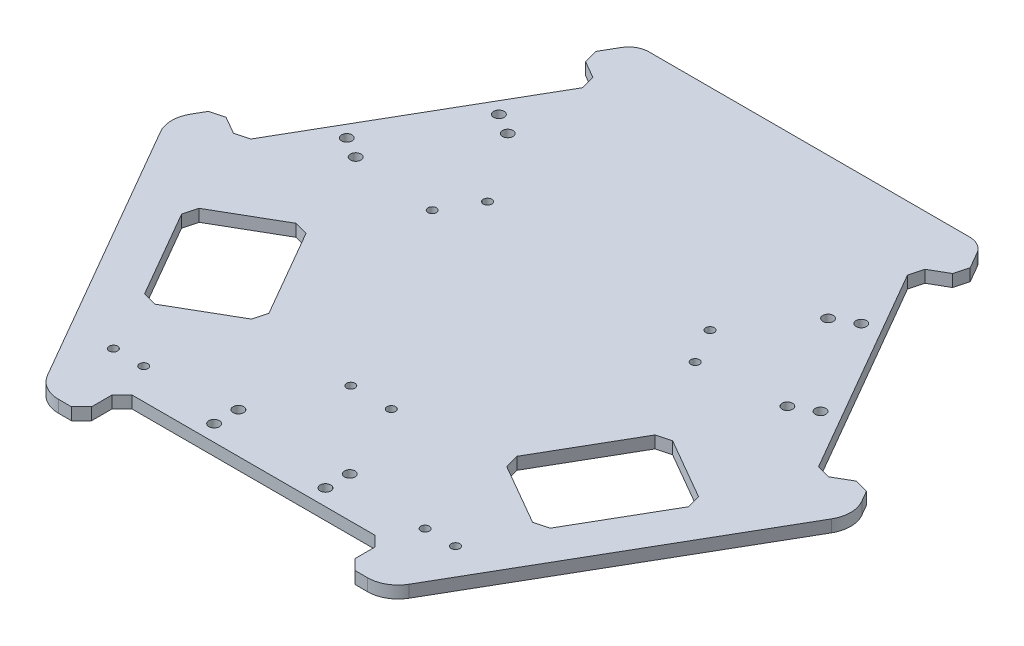
SolidWorks part; units mm, degrees
material "5052-H32"
ref_plane "前基準面" through (0, 0, 0) normal (0, 0, 1) x (1, 0, 0)
ref_plane "上基準面" through (0, 0, 0) normal (0, 1, 0) x (1, 0, 0)
ref_plane "右基準面" through (0, 0, 0) normal (1, 0, 0) x (0, 0, -1)
sketch "草圖1" plane through (0, 0, 0) normal (0, 1, 0) x (1, 0, 0)
  line L1 (85, 147.2243) -> (-85, 147.2243)
  line L2 (-85, 147.2243) -> (-170, 0)
  line L3 (-170, 0) -> (-85, -147.2243)
  line L4 (-85, -147.2243) -> (85, -147.2243)
  line L5 (85, -147.2243) -> (170, 0)
  line L6 (170, 0) -> (85, 147.2243)
  circle A0 centre (0, 0) radius 147.2243 construction
  dimension "D1" = 170
extrude "填料-伸長1" add sketch "草圖1" along normal blind 6
ref_axis "基準軸1" through (0, 5.25, 0) along (0, -1, 0)
sketch "草圖16" plane through (0, 6, 0) normal (0, 1, 0) x (1, 0, 0)
  line L0 (-65, -147.2243) -> (65, -147.2243)
  line L1 (-65, -147.2243) -> (-65, -127.2243)
  line L2 (65, -147.2243) -> (65, -127.2243)
  line L3 (-65, -127.2243) -> (65, -127.2243)
  line L4 (-85, -147.2243) -> (85, -147.2243) construction
  point P6 (0, -147.2243)
  point P7 (0, -147.2243)
  dimension "D1" = 20
  dimension "D2" = 130
extrude "除料-伸長16" cut sketch "草圖16" against normal blind 10
sketch "草圖9" plane through (0, 6, 0) normal (0, 1, 0) x (1, 0, 0)
  line L0 (-27.5, -107.2243) -> (27.5, -107.2243) construction
  line L1 (27.5, -107.2243) -> (27.5, -119.2243) construction
  line L2 (-27.5, -107.2243) -> (-27.5, -119.2243) construction
  line L3 (-27.5, -119.2243) -> (27.5, -119.2243) construction
  line L4 (65, -127.2243) -> (-65, -127.2243) construction
  circle A0 centre (-27.5, -119.2243) radius 2.6
  circle A1 centre (-27.5, -107.2243) radius 2.6
  circle A2 centre (27.5, -107.2243) radius 2.6
  circle A3 centre (27.5, -119.2243) radius 2.6
  point P8 (-36.6057, -114.7334)
  point P11 (0, -119.2243)
  point P12 (0, -127.2243)
  dimension "D1" = 5.2
  dimension "D2" = 12
  dimension "D3" = 8
  dimension "D4" = 55
extrude "除料-伸長8" cut sketch "草圖9" against normal through all and the other way through all
sketch "草圖18" plane through (0, 6, 0) normal (0, 1, 0) x (1, 0, 0)
  line L0 (-10, -69.2243) -> (10, -69.2243) construction
  line L1 (65, -127.2243) -> (-65, -127.2243) construction
  circle A0 centre (-10, -69.2243) radius 2.1
  circle A1 centre (10, -69.2243) radius 2.1
  point P4 (0, -69.2243)
  point P7 (0, -127.2243)
  dimension "D3" = 4.2
  dimension "D4" = 4.2
  dimension "D1" = 20
  dimension "D2" = 58
extrude "除料-伸長17" cut sketch "草圖18" against normal up to next
pattern_circular "環狀複製排列1" count 3 over 360 about axis through (0, 5.25, 0) along (0, -1, 0) of "除料-伸長8", "除料-伸長16", "除料-伸長17"
chamfer "導角4" distance 5 angle 45 12 edges at (65, 3, 127.2243) (65, 3, 147.2243) (-65, 3, 147.2243) (-65, 3, 127.2243) (77.6795, 3, -119.9038) (95, 3, -129.9038) (160, 3, -17.3205) (142.6795, 3, -7.3205) (-142.6795, 3, -7.3205) (-160, 3, -17.3205) (-95, 3, -129.9038) (-77.6795, 3, -119.9038)
sketch "草圖5" plane through (0, 6, 0) normal (0, 1, 0) x (1, 0, 0)
  line L0 (0, 0) -> (0, -112) construction
  line L1 (0, -112) -> (-77, -112) construction
  line L2 (-84.5, -112) -> (-69.5, -112) construction
  circle A0 centre (-84.5, -112) radius 2.1
  circle A1 centre (-69.5, -112) radius 2.1
  circle A2 centre (84.5, -112) radius 2.1
  circle A3 centre (69.5, -112) radius 2.1
  point P8 (-77, -112)
  dimension "D1" = 4.2
  dimension "D2" = 15
  dimension "D3" = 112
  dimension "D4" = 77
extrude "除料-伸長5" cut sketch "草圖5" against normal through all
sketch "草圖8" plane through (0, 6, 0) normal (0, 1, 0) x (1, 0, 0)
  line L0 (-127.6795, -33.3013) -> (-97.6795, -85.2628)
  line L1 (-127.6795, -33.3013) -> (-88.7083, -10.8013)
  line L2 (-97.6795, -85.2628) -> (-58.7083, -62.7628)
  line L3 (-88.7083, -10.8013) -> (-58.7083, -62.7628)
  line L5 (-170, 0) -> (-85, -147.2243) construction
  line L6 (-170, 0) -> (-145, -43.3013) construction
  line L7 (-145, -43.3013) -> (-127.6795, -33.3013) construction
  dimension "D1" = 45
  dimension "D2" = 60
  dimension "D3" = 20
  dimension "D4" = 50
extrude "除料-伸長7" cut sketch "草圖8" against normal through all
chamfer "導角2" distance 5 angle 45 4 edges at (-58.7083, 3, 62.7628) (-97.6795, 3, 85.2628) (-127.6795, 3, 33.3013) (-88.7083, 3, 10.8013)
mirror "鏡射1" about plane through (0, 0, 0) normal (1, 0, 0) of "除料-伸長7", "導角2"
fillet "圓角2" radius 15 4 edges at (-170, 3, 0) (-85, 3, 147.2243) (85, 3, 147.2243) (170, 3, 0)
fillet "圓角3" radius 10 2 edges at (85, 3, -147.2243) (-85, 3, -147.2243)
